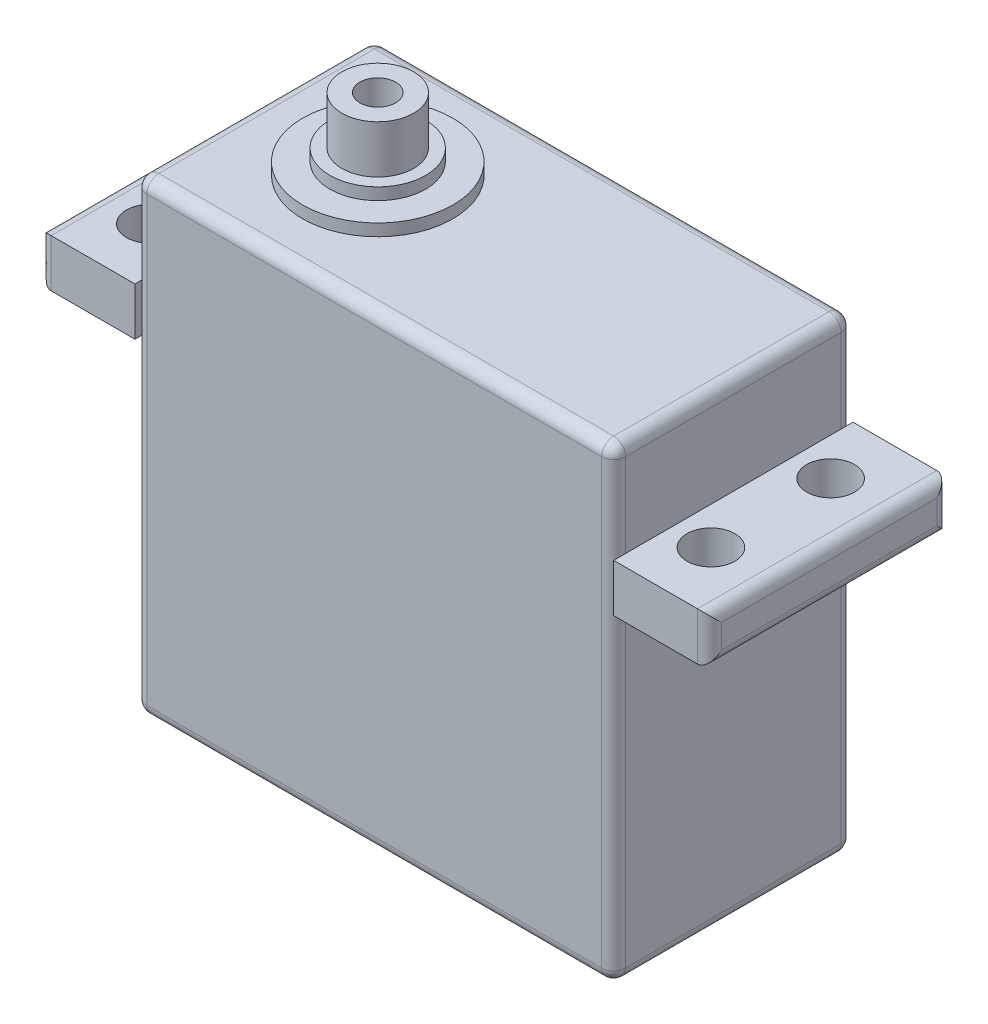
SolidWorks part; units mm, degrees
ref_plane "前视基准面" through (0, 0, 0) normal (0, 0, 1) x (1, 0, 0)
ref_plane "上视基准面" through (0, 0, 0) normal (0, 1, 0) x (1, 0, 0)
ref_plane "右视基准面" through (0, 0, 0) normal (1, 0, 0) x (0, 0, -1)
other "Configuration Table"
sketch "草图1" plane through (0, 0, 0) normal (0, 0, 1) x (1, 0, 0)
  line L1 (-20, 19.5) -> (20, 19.5)
  line L2 (-20, 19.5) -> (-20, -19.5)
  line L3 (-20, -19.5) -> (20, -19.5)
  line L4 (20, 19.5) -> (20, -19.5)
  line L5 (-20, 19.5) -> (20, -19.5) construction
  line L6 (-20, -19.5) -> (20, 19.5) construction
  point P0 (0, 0)
  dimension "D1" = 39
  dimension "D2" = 40
extrude "凸台-拉伸1" add sketch "草图1" along normal blind 20
fillet "圆角1" radius 1 12 edges at (-20, 0, 0) (-20, -19.5, 10) (0, -19.5, 0) (20, -19.5, 10) (20, 0, 0) (20, 19.5, 10) (-20, 19.5, 10) (0, 19.5, 0) (0, -19.5, 20) (-20, 0, 20) (0, 19.5, 20) (20, 0, 20)
sketch "草图2" plane through (20, 0, 0) normal (1, 0, 0) x (0, 0, -1)
  line L0 (-20, -18.5) -> (-20, 18.5) construction
  line L1 (-20, 11.5) -> (0, 11.5)
  line L2 (-20, 11.5) -> (-20, 7.5)
  line L3 (-20, 7.5) -> (0, 7.5)
  line L4 (0, 11.5) -> (0, 7.5)
  line L5 (0, 18.5) -> (0, -18.5) construction
  line L6 (-1, -19.5) -> (-19, -19.5) construction
  dimension "D1" = 31
  dimension "D2" = 4
extrude "凸台-拉伸2" add sketch "草图2" along normal blind 8 contours L2 L1 L4 L3
fillet "圆角4" radius 1 4 edges at (28, 9.5, 20) (28, 11.5, 10) (28, 9.5, 0) (28, 7.5, 10)
sketch "草图3" plane through (-20, 0, 0) normal (-1, 0, 0) x (0, 0, 1)
  line L0 (0, -18.5) -> (0, 18.5) construction
  line L1 (20, 18.5) -> (20, -18.5) construction
  line L2 (0, 11.5) -> (20, 11.5)
  line L3 (0, 11.5) -> (0, 7.5)
  line L4 (0, 7.5) -> (20, 7.5)
  line L5 (20, 11.5) -> (20, 7.5)
  line L6 (19, -19.5) -> (1, -19.5) construction
  dimension "D1" = 31
  dimension "D2" = 4
extrude "凸台-拉伸3" add sketch "草图3" along normal blind 8 contours L3 L2 L5 L4
fillet "圆角5" radius 1 4 edges at (-28, 9.5, 0) (-28, 11.5, 10) (-28, 9.5, 20) (-28, 7.5, 10)
sketch "草图4" plane through (0, 19.5, 0) normal (0, 1, 0) x (1, 0, 0)
  circle A0 centre (-11.7646, -9.5602) radius 3
  dimension "D1" = 6
sketch "草图5" plane through (0, 11.5, 0) normal (0, 1, 0) x (1, 0, 0)
  line L0 (-20, -10) -> (-33.2491, -10) construction
  line L2 (-20, -1) -> (-20, -19) construction
  circle A1 centre (-23.7124, -15) radius 2
  circle A2 centre (-23.7124, -5) radius 2
  dimension "D1" = 5
  dimension "D2" = 4
extrude "切除-拉伸2" cut sketch "草图5" against normal blind 4
sketch "草图13" plane through (0, 11.5, 0) normal (0, 1, 0) x (1, 0, 0)
  line L0 (20, -10) -> (30.456, -10) construction
  line L1 (20, -19) -> (20, -1) construction
  circle A0 centre (23.126, -5) radius 2
  circle A1 centre (23.126, -15) radius 2
  dimension "D2" = 4
  dimension "D1" = 5
extrude "切除-拉伸3" cut sketch "草图13" against normal blind 4
sketch "草图14" plane through (0, 19.5, 0) normal (0, 1, 0) x (1, 0, 0)
  circle A0 centre (-11.7646, -9.5602) radius 3
  point P4 (-11.7646, -9.5602)
sketch "草图17" plane through (0, 19.5, 0) normal (0, 1, 0) x (1, 0, 0)
  circle A0 centre (-23.7124, -5) radius 2
  circle A1 centre (-9.7124, -10) radius 5.864
  circle A2 centre (-9.7124, -10) radius 4.1239
  circle A3 centre (-9.7124, -10) radius 3
  dimension "D2" = 6
  dimension "D1" = 14
extrude "凸台-拉伸8" add sketch "草图17" along normal blind 6 contours A3 region at (-9.7124, 19.5, 10)
sketch "草图21" plane through (0, 19.5, 0) normal (0, 1, 0) x (1, 0, 0)
  circle A0 centre (-9.7124, -10) radius 6.2822
  circle A1 centre (-9.7124, -10) radius 4
  circle A2 centre (-23.7124, -5) radius 2
  dimension "D1" = 8
  dimension "D2" = 12.5644
extrude "凸台-拉伸9" add sketch "草图21" along normal blind 1 contours A0 | A1
sketch "草图22" plane through (0, 19.5, 0) normal (0, 1, 0) x (1, 0, 0)
  circle A0 centre (-9.7124, -10) radius 4
  circle A1 centre (-9.7124, -10) radius 3
extrude "凸台-拉伸10" add sketch "草图22" along normal blind 2 contours A0
sketch "草图27" plane through (0, 19.5, 0) normal (0, 1, 0) x (1, 0, 0)
  circle A0 centre (-9.7124, -10) radius 1.5
  dimension "D1" = 3
sketch "草图28" plane through (0, 25.5, 0) normal (0, 1, 0) x (1, 0, 0)
  circle A0 centre (-9.7124, -10) radius 1.5
extrude "切除-拉伸4" cut sketch "草图28" against normal blind 6
